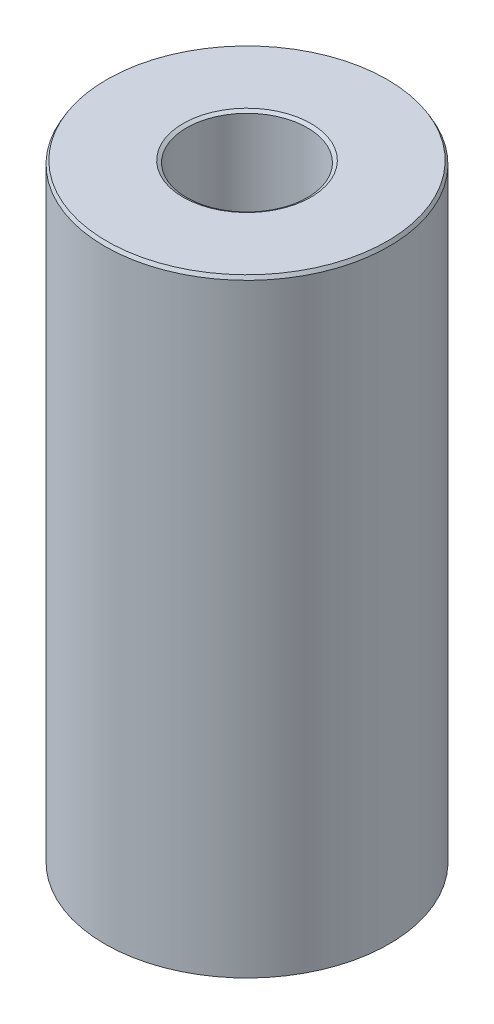
SolidWorks part; units mm, degrees
ref_plane "Front Plane" through (0, 0, 0) normal (0, 0, 1) x (1, 0, 0)
ref_plane "Top Plane" through (0, 0, 0) normal (0, 1, 0) x (1, 0, 0)
ref_plane "Right Plane" through (0, 0, 0) normal (1, 0, 0) x (0, 0, -1)
sketch "Sketch1" plane through (0, 0, 0) normal (0, 1, 0) x (1, 0, 0)
  circle A0 centre (0, 0) radius 32.5
  dimension "SLEEVE_OD" = 65
extrude "Boss-Extrude1" add sketch "Sketch1" along normal blind 139.3983
sketch "Sketch2" plane through (0, 0, 0) normal (0, 1, 0) x (1, 0, 0)
  circle A0 centre (0, 0) radius 13.8266
  dimension "BORE_D" = 27.6532
extrude "Cut-Extrude1" cut sketch "Sketch2" along normal through all
chamfer "Chamfer1" distance 0.7878 angle 30 4 edges at (0, 139.3983, 13.8266) (0, 0, 13.8266) (0, 0, 32.5) (0, 139.3983, 32.5) first distance on face at (0, 139.3983, 13.8266) first distance on face at (0, 0, 13.8266) first distance on face at (0, 139.3983, 32.5)
